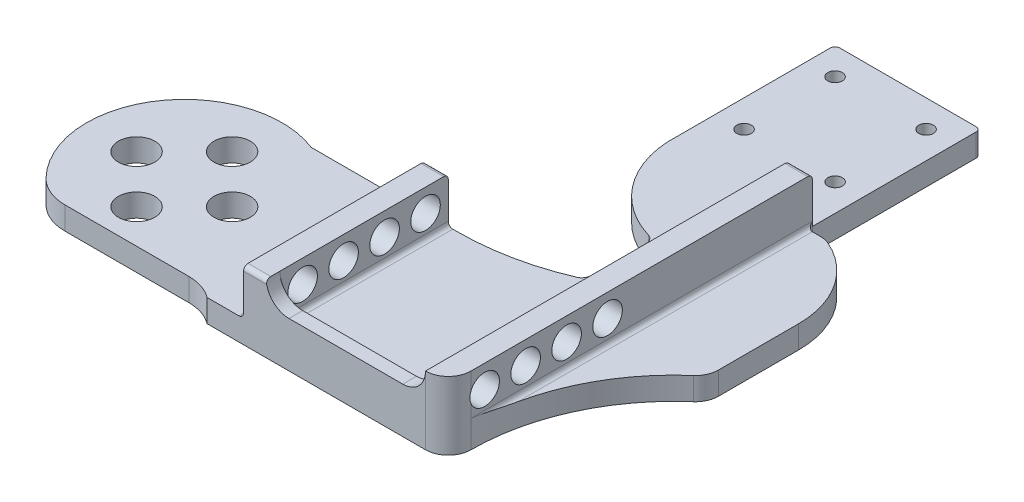
SolidWorks part; units mm, degrees
ref_plane "Спереди" through (0, 0, 0) normal (0, 0, 1) x (1, 0, 0)
ref_plane "Сверху" through (0, 0, 0) normal (0, 1, 0) x (1, 0, 0)
ref_plane "Справа" through (0, 0, 0) normal (1, 0, 0) x (0, 0, -1)
sketch "Эскиз2" plane through (0, 0, 0) normal (0, 1, 0) x (1, 0, 0)
  line L0 (0, 0) -> (32, 0)
  line L1 (0, 0) -> (0, 88)
  line L2 (32, 0) -> (32, 88)
  line L3 (0, 88) -> (32, 88)
  dimension "D1" = 88
  dimension "D2" = 32
extrude "Бобышка-Вытянуть1" add sketch "Эскиз2" along normal blind 5
sketch "Эскиз9" plane through (0, 5, 0) normal (0, 1, 0) x (1, 0, 0)
  line L0 (32, 10) -> (32, -30)
  line L1 (32, 10) -> (-68, 10)
  line L2 (32, -30) -> (-68, -30)
  line L3 (-68, 10) -> (-68, -30)
  line L4 (32, 0) -> (32, 88) construction
  line L5 (-68, -10) -> (32, -10) construction
  line L6 (32, 88) -> (0, 88) construction
  dimension "D1" = 98
  dimension "D2" = 40
  dimension "D3" = 100
extrude "Бобышка-Вытянуть6" add sketch "Эскиз9" against normal blind 5
sketch "Эскиз11" plane through (0, 5, 0) normal (0, 1, 0) x (1, 0, 0)
  line L0 (-46, -10) -> (-46, -20.5) construction
  line L1 (-46, -10) -> (-46, 0.5) construction
  line L6 (-68, -10) -> (32, -10) construction
  line L7 (-68, 10) -> (-68, -30) construction
  line L8 (32, -30) -> (32, 88) construction
  circle A0 centre (-46, -10) radius 10.5 construction
  circle A1 centre (-46, 0.5) radius 4
  circle A2 centre (-35.5, -10) radius 4
  circle A3 centre (-46, -20.5) radius 4
  circle A4 centre (-56.5, -10) radius 4
  dimension "D1" = 22
  dimension "D3" = 21
  dimension "D4" = 8
  dimension "D5" = 8
  dimension "D6" = 8
  dimension "D2" = 8
extrude "Вырез-Вытянуть3" cut sketch "Эскиз11" against normal up to surface (5 mm away) up to face at (-12, 0, -22.6667)
sketch "Эскиз12" plane through (0, 0, 0) normal (0, -1, 0) x (1, 0, 0)
  circle A4 centre (-46, 20.5) radius 4 construction
  circle A5 centre (-35.5, 10) radius 4 construction
  circle A6 centre (-46, -0.5) radius 4 construction
  circle A7 centre (-56.5, 10) radius 4 construction
  circle A8 centre (-46, 10) radius 19.5
  circle A9 centre (-46, 10) radius 21.5
  circle A10 centre (-46, 20.5) radius 4 construction
  circle A11 centre (-35.5, 10) radius 4 construction
  circle A12 centre (-46, -0.5) radius 4 construction
  circle A13 centre (-56.5, 10) radius 4 construction
  circle A14 centre (-46, 10) radius 10.5 construction
  dimension "D1" = 39
  dimension "D2" = 43
extrude "Бобышка-Вытянуть7" add sketch "Эскиз12" along normal blind 8
sketch "Эскиз13" plane through (0, 5, 0) normal (0, 1, 0) x (1, 0, 0)
  line L0 (6, 81) -> (26, 81) construction
  line L1 (6, 81) -> (6, 61) construction
  line L2 (26, 81) -> (26, 61) construction
  line L3 (6, 61) -> (26, 61) construction
  line L4 (16, 81) -> (16, 61) construction
  line L5 (16, 88) -> (16, -30) construction
  line L6 (32, 88) -> (0, 88) construction
  line L7 (-68, -30) -> (32, -30) construction
  circle A0 centre (6, 81) radius 1.6
  circle A1 centre (6, 61) radius 1.6
  circle A2 centre (26, 61) radius 1.6
  circle A3 centre (26, 81) radius 1.6
  dimension "D4" = 3.2
  dimension "D5" = 3.2
  dimension "D6" = 3.2
  dimension "D7" = 3.2
  dimension "D1" = 20
  dimension "D2" = 20
  dimension "D3" = 7
extrude "Вырез-Вытянуть4" cut sketch "Эскиз13" against normal through all
sketch "Sketch1" plane through (0, 0, -88) normal (0, 0, -1) x (-1, 0, 0)
  line L4 (-32, 0) -> (0, 0)
  line L5 (0, 0) -> (0, 5)
  line L6 (0, 5) -> (-32, 5)
  line L7 (-32, 5) -> (-32, 0)
  line L8 (-32, 0) -> (0, 0)
  line L9 (0, 0) -> (0, 5)
  line L10 (0, 5) -> (-32, 5)
  line L11 (-32, 5) -> (-32, 0)
  dimension "D1" = 0
extrude "Cut-Extrude1" cut sketch "Sketch1" against normal blind 1
sketch "Эскиз14" plane through (0, 0, 0) normal (0, -1, 0) x (1, 0, 0)
  line L3 (-53.8899, 30) -> (-68, 30)
  line L4 (-68, 30) -> (-68, -10)
  line L5 (-68, -10) -> (-53.8899, -10)
  line L6 (-53.8899, 30) -> (-68, 30)
  line L7 (-68, 30) -> (-68, -10)
  line L8 (-68, -10) -> (-53.8899, -10)
  arc A1 (-53.8899, 30) -> (-53.8899, -10) centre (-46, 10) ccw
  arc A2 (-53.8899, 30) -> (-53.8899, -10) centre (-46, 10) ccw
  dimension "D1" = 0
extrude "Вырез-Вытянуть5" cut sketch "Эскиз14" against normal through all
sketch "Эскиз15" plane through (0, 0, 0) normal (0, 1, 0) x (1, 0, 0)
  line L1 (-38.1101, -30) -> (-53.8899, -30)
  line L2 (-38.1101, -30) -> (-53.8899, -30)
  line L3 (-53.8899, 10) -> (-38.1101, 10)
  line L4 (-53.8899, 10) -> (-38.1101, 10)
  arc A1 (-53.8899, -30) -> (-38.1101, -30) centre (-46, -10) ccw
  arc A2 (-53.8899, -30) -> (-38.1101, -30) centre (-46, -10) ccw
  arc A3 (-38.1101, 10) -> (-53.8899, 10) centre (-46, -10) ccw
  arc A4 (-38.1101, 10) -> (-53.8899, 10) centre (-46, -10) ccw
  dimension "D1" = 0
  dimension "D2" = 0
extrude "Бобышка-Вытянуть8" add sketch "Эскиз15" along normal up to surface (5 mm away) up to face at (-46, 5, 3.5)
sketch "Эскиз16" plane through (0, 5, 0) normal (0, 1, 0) x (1, 0, 0)
  line L0 (-13, 10) -> (-8, 10)
  line L1 (-13, 10) -> (-13, -30)
  line L2 (-8, 10) -> (-8, -30)
  line L3 (-13, -30) -> (-8, -30)
  line L4 (0, 10) -> (-38.1101, 10) construction
  line L5 (-38.1101, -30) -> (32, -30) construction
  line L6 (32, -30) -> (32, 87) construction
  line L7 (27, -30) -> (32, -30)
  line L8 (27, -30) -> (27, 50)
  line L9 (32, -30) -> (32, 50)
  line L10 (27, 50) -> (32, 50)
  dimension "D1" = 5
  dimension "D2" = 45
  dimension "D3" = 5
  dimension "D4" = 80
extrude "Бобышка-Вытянуть9" add sketch "Эскиз16" along normal blind 10
sketch "Эскиз17" plane through (0, 5, 0) normal (0, 1, 0) x (1, 0, 0)
  line L0 (-8, -30) -> (-8, -27)
  line L1 (-8, -30) -> (27, -30)
  line L2 (-8, -27) -> (27, -27)
  line L3 (27, -30) -> (27, -27)
  line L4 (-8, -30) -> (-8, 10) construction
  line L5 (27, 50) -> (27, -30) construction
  dimension "D1" = 3
extrude "Бобышка-Вытянуть10" add sketch "Эскиз17" along normal blind 5
sketch "Эскиз18" plane through (-8, 0, 0) normal (1, 0, 0) x (0, 0, -1)
  line L0 (10, 10) -> (-41.8716, 10) construction
  line L1 (10, 15) -> (10, 5) construction
  circle A0 centre (5, 10) radius 3.25
  circle A1 centre (-4, 10) radius 3.25
  circle A2 centre (-13, 10) radius 3.25
  circle A3 centre (-22, 10) radius 3.25
  dimension "D1" = 6.5
  dimension "D2" = 6.5
  dimension "D3" = 6.5
  dimension "D4" = 6.5
  dimension "D5" = 5
  dimension "D6" = 9
  dimension "D7" = 9
  dimension "D8" = 9
extrude "Вырез-Вытянуть6" cut sketch "Эскиз18" against normal through all
sketch "Эскиз19" plane through (32, 0, 0) normal (1, 0, 0) x (0, 0, -1)
  line L0 (50, 10) -> (-21.4049, 10) construction
  line L1 (50, 15) -> (50, 5) construction
  circle A0 centre (41, 10) radius 3.25
  circle A1 centre (32, 10) radius 3.25
  circle A2 centre (23, 10) radius 3.25
  circle A3 centre (14, 10) radius 3.25
  dimension "D1" = 6.5
  dimension "D2" = 6.5
  dimension "D3" = 6.5
  dimension "D4" = 6.5
  dimension "D5" = 9
  dimension "D6" = 9
  dimension "D7" = 9
  dimension "D8" = 9
fillet "Скругление5" radius 1 4 edges at (27, 5, -11.5) (9.5, 5, 27)
fillet "Скругление6" radius 5 2 edges at (27, 10, 28.5) (-8, 10, 28.5)
fillet "Скругление7" radius 1 2 edges at (32, 2.5, -87) (0, 2.5, -87)
fillet "Скругление8" radius 1 3 edges at (-10.5, 15, 30) (-10.5, 15, -10) (29.5, 15, -50)
sketch "Эскиз20" plane through (0, -8, 0) normal (0, -1, 0) x (1, 0, 0)
  circle A1 centre (-46, 10) radius 21.5
  circle A2 centre (-46, 10) radius 21.5
  dimension "D1" = 0
extrude "Вырез-Вытянуть8" cut sketch "Эскиз20" against normal up to surface (8 mm away) up to face at (-46, 0, -4.5)
sketch "Эскиз21" plane through (0, 5, 0) normal (0, 1, 0) x (1, 0, 0)
  line L0 (-57.758, -28) -> (-27, -28)
  line L1 (-38.1101, -30) -> (-14, -30) construction
  line L2 (-13, 10) -> (-13, -30) construction
  line L3 (-38.1101, -30) -> (-21, -30)
  arc A0 (-38.1101, 10) -> (-38.1101, -30) centre (-46, -10) ccw construction
  arc A1 (-27, -28) -> (-21, -30) centre (-27, -38) cw
  arc A2 (-57.758, -28) -> (-38.1101, -30) centre (-46, -10) ccw
  dimension "D1" = 2
  dimension "D2" = 10
  dimension "D3" = 8
extrude "Вырез-Вытянуть9" cut sketch "Эскиз21" against normal through all
fillet "Скругление9" radius 10 1 edges at (-57.758, 2.5, 28)
sketch "Эскиз22" plane through (0, 0, 0) normal (-1, 0, 0) x (0, 0, 1)
  line L0 (-50, 14) -> (-50, 6) construction
  line L1 (-50, 5) -> (-50, 0) construction
  line L2 (-86, 5) -> (-10, 5) construction
  line L3 (-86, 0) -> (-10, 0) construction
  line L4 (-50, 5) -> (-10, 5)
  line L5 (-50, 0) -> (-10, 0)
  line L6 (-10, 0) -> (-10, 5) construction
  line L7 (-10, 0) -> (-10, 5)
  line L8 (-50, 5) -> (-50, 0)
extrude "Вырез-Вытянуть10" cut sketch "Эскиз22" against normal blind 17
sketch "Эскиз23" plane through (32, 0, 0) normal (1, 0, 0) x (0, 0, -1)
  line L4 (10, 5) -> (10, 0)
  line L5 (50, 5) -> (10, 5)
  line L6 (50, 0) -> (50, 5)
  line L7 (10, 0) -> (50, 0)
  line L8 (10, 5) -> (10, 0)
  line L9 (50, 5) -> (10, 5)
  line L10 (50, 0) -> (50, 5)
  line L11 (10, 0) -> (50, 0)
  dimension "D1" = 0
extrude "Бобышка-Вытянуть11" add sketch "Эскиз23" along normal blind 17
sketch "Эскиз25" plane through (0, 5, 0) normal (0, 1, 0) x (1, 0, 0)
  line L0 (17, 15) -> (17, 10)
  line L1 (17, 10) -> (17, 50) construction
  line L2 (17, 10) -> (-6, 10)
  line L3 (17, 10) -> (-7, 10) construction
  line L6 (17, 30) -> (17, 50)
  line L7 (17, 50) -> (0, 50)
  arc A0 (17, 30) -> (0, 50) centre (21.9531, 51.4352) cw
  arc A1 (17, 15) -> (-6, 10) centre (-6, 65.4) cw
  dimension "D4" = 22
  dimension "D1" = 5
  dimension "D2" = 23
  dimension "D3" = 15
  dimension "D5" = 20
extrude "Бобышка-Вытянуть12" add sketch "Эскиз25" against normal up to surface (5 mm away) up to face at (4.4666, 0, -26.743)
fillet "Скругление10" radius 2 2 edges at (17, 2.5, -15) (17, 2.5, -30)
sketch "Эскиз26" plane through (0, 5, 0) normal (0, 1, 0) x (1, 0, 0)
  line L0 (32, 30) -> (49, 30) construction
  line L1 (32, 50) -> (32, 10) construction
  line L3 (49, 50) -> (49, 10) construction
  line L4 (32, 50) -> (32, 30) construction
  line L5 (49, 50) -> (32, 50) construction
  line L6 (49, 50) -> (32, 50)
  line L7 (49, 50) -> (49, 30)
  arc A0 (49, 30) -> (32, 50) centre (28.7353, 30) ccw
  dimension "D1" = 20
extrude "Вырез-Вытянуть11" cut sketch "Эскиз26" against normal through all
sketch "Эскиз27" plane through (0, 5, 0) normal (0, 1, 0) x (1, 0, 0)
  line L0 (49, 10) -> (32, 10) construction
  line L1 (49, 10) -> (32, 10)
  line L2 (32, 10) -> (32, -25)
  arc A0 (49, 10) -> (32, -25) centre (76.5294, -25) ccw
  dimension "D1" = 35
extrude "Бобышка-Вытянуть13" add sketch "Эскиз27" against normal up to surface (5 mm away) up to face at (5.1363, 0, -23.6939)
fillet "Скругление12" radius 5 1 edges at (32, 7.5, 30)
fillet "Скругление13" radius 1 1 edges at (32, 5, -12.5)
sketch "Эскиз28" plane through (32, 0, 0) normal (1, 0, 0) x (0, 0, -1)
  circle A0 centre (5, 10) radius 3.25 construction
  circle A1 centre (-4, 10) radius 3.25 construction
  circle A2 centre (-13, 10) radius 3.25 construction
  circle A3 centre (-22, 10) radius 3.25 construction
  circle A4 centre (5, 10) radius 3.25
  circle A5 centre (-4, 10) radius 3.25
  circle A6 centre (-13, 10) radius 3.25
  circle A7 centre (-22, 10) radius 3.25
extrude "Вырез-Вытянуть12" cut sketch "Эскиз28" against normal up to surface (5 mm away) up to face at (27, 11.2414, -19.0414)
fillet "Скругление14" radius 5 1 edges at (49, 2.5, -10)
sketch "Эскиз29" plane through (0, 0, -50) normal (0, 0, -1) x (-1, 0, 0)
  line L0 (-32, 0) -> (-32, 5) construction
  line L1 (-32, 0) -> (-32, 8)
  line L2 (-32, 14) -> (-32, 6) construction
  line L3 (-32, 8) -> (-37, 8)
  line L4 (-37, 8) -> (-37, 0)
  line L5 (-37, 0) -> (-32, 0)
  dimension "D1" = 5
  dimension "D2" = 8
extrude "Вырез-Вытянуть13" cut sketch "Эскиз29" against normal blind 1
fillet "Скругление15" radius 1 1 edges at (32, 3, -49)
fillet "Скругление16" radius 5 1 edges at (35.7822, 2.5, -49)
